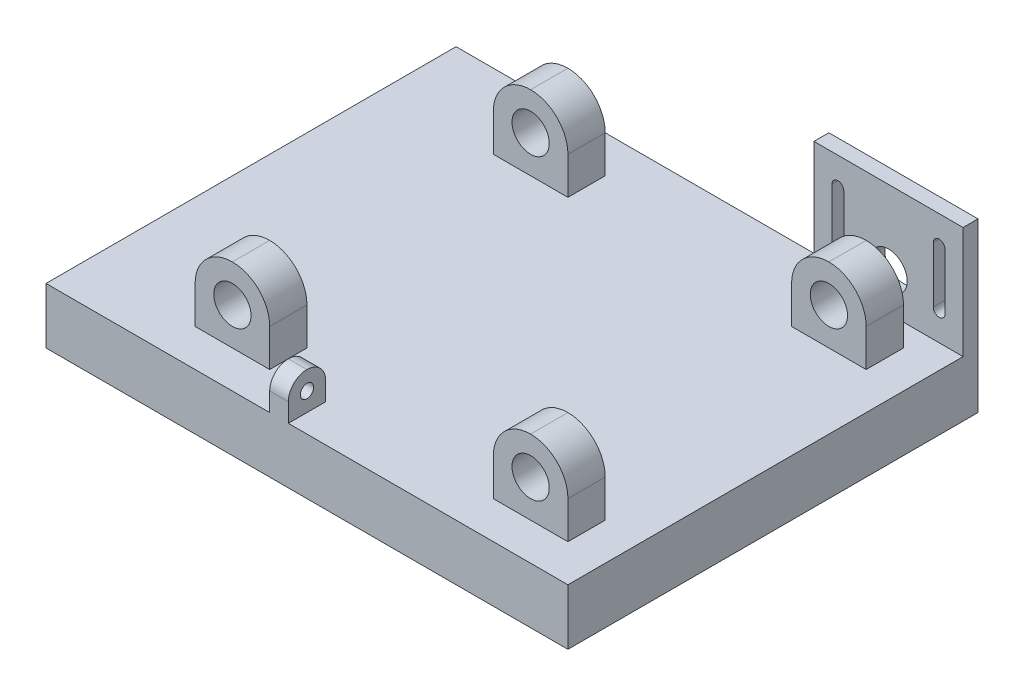
SolidWorks part; units mm, degrees
ref_plane "Front Plane" through (0, 0, 0) normal (0, 0, 1) x (1, 0, 0)
ref_plane "Top Plane" through (0, 0, 0) normal (0, 1, 0) x (1, 0, 0)
ref_plane "Right Plane" through (0, 0, 0) normal (1, 0, 0) x (0, 0, -1)
sketch "Sketch1" plane through (0, 0, 0) normal (0, 1, 0) x (1, 0, 0)
  line L1 (-88.9, -69.85) -> (88.9, -69.85)
  line L2 (-88.9, -69.85) -> (-88.9, 69.85)
  line L3 (-88.9, 69.85) -> (88.9, 69.85)
  line L4 (88.9, -69.85) -> (88.9, 69.85)
  line L5 (-88.9, -69.85) -> (88.9, 69.85) construction
  line L6 (-88.9, 69.85) -> (88.9, -69.85) construction
  point P0 (0, 0)
  dimension "D1" = 177.8
  dimension "D2" = 139.7
extrude "Boss-Extrude1" add sketch "Sketch1" along normal blind 19.05
sketch "Sketch3" plane through (0, 19.05, 0) normal (0, 1, 0) x (1, 0, 0)
  line L0 (-88.9, -69.85) -> (88.9, -69.85) construction
  line L1 (-50.8, 57.15) -> (-25.4, 57.15)
  line L2 (-50.8, 57.15) -> (-50.8, 44.45)
  line L3 (-50.8, 44.45) -> (-25.4, 44.45)
  line L4 (-25.4, 57.15) -> (-25.4, 44.45)
  line L5 (-50.8, 57.15) -> (-25.4, 44.45) construction
  line L6 (-50.8, 44.45) -> (-25.4, 57.15) construction
  line L7 (50.8, 57.15) -> (76.2, 57.15)
  line L8 (50.8, 57.15) -> (50.8, 44.45)
  line L9 (50.8, 44.45) -> (76.2, 44.45)
  line L10 (76.2, 57.15) -> (76.2, 44.45)
  line L11 (50.8, 57.15) -> (76.2, 44.45) construction
  line L12 (50.8, 44.45) -> (76.2, 57.15) construction
  line L13 (88.9, 69.85) -> (-88.9, 69.85) construction
  line L14 (-88.9, 69.85) -> (-88.9, -69.85) construction
  line L15 (88.9, -69.85) -> (88.9, 69.85) construction
  line L19 (-50.8, -44.45) -> (-25.4, -44.45)
  line L20 (-50.8, -44.45) -> (-50.8, -57.15)
  line L21 (-50.8, -57.15) -> (-25.4, -57.15)
  line L22 (-25.4, -44.45) -> (-25.4, -57.15)
  line L23 (-50.8, -44.45) -> (-25.4, -57.15) construction
  line L24 (-50.8, -57.15) -> (-25.4, -44.45) construction
  line L25 (50.8, -57.15) -> (76.2, -57.15)
  line L26 (50.8, -57.15) -> (50.8, -44.45)
  line L27 (50.8, -44.45) -> (76.2, -44.45)
  line L28 (76.2, -57.15) -> (76.2, -44.45)
  line L29 (50.8, -57.15) -> (76.2, -44.45) construction
  line L30 (50.8, -44.45) -> (76.2, -57.15) construction
  point P0 (-38.1, 50.8)
  point P5 (63.5, 50.8)
  point P10 (46.38, 48.3675)
  point P15 (-38.1, -50.8)
  point P20 (63.5, -50.8)
  dimension "D1" = 25.4
  dimension "D2" = 12.7
  dimension "D3" = 12.7
  dimension "D4" = 12.7
  dimension "D5" = 38.1
  dimension "D6" = 38.1
  dimension "D7" = 12.7
  dimension "D8" = 12.7
  dimension "D9" = 25.4
  dimension "D10" = 12.7
extrude "Boss-Extrude2" add sketch "Sketch3" along normal blind 25.4
sketch "Sketch5" plane through (0, 19.05, 0) normal (0, 1, 0) x (1, 0, 0)
  line L0 (88.9, -69.85) -> (88.9, 69.85) construction
  line L1 (38.1, 64.77) -> (88.9, 64.77)
  line L2 (38.1, 64.77) -> (38.1, 69.85)
  line L3 (38.1, 69.85) -> (88.9, 69.85)
  line L4 (88.9, 64.77) -> (88.9, 69.85)
  line L5 (38.1, 64.77) -> (88.9, 69.85) construction
  line L6 (38.1, 69.85) -> (88.9, 64.77) construction
  line L7 (88.9, 69.85) -> (-88.9, 69.85) construction
  point P0 (63.5, 67.31)
  dimension "D1" = 50.8
  dimension "D2" = 0
  dimension "D3" = 5.08
  dimension "D4" = 0
extrude "Boss-Extrude3" add sketch "Sketch5" along normal blind 38.1
sketch "Sketch4" plane through (0, 0, 44.45) normal (0, 0, -1) x (-1, 0, 0)
  line L0 (50.8, 44.45) -> (25.4, 44.45) construction
  line L1 (25.4, 44.45) -> (25.4, 19.05) construction
  line L2 (-76.2, 44.45) -> (-76.2, 19.05) construction
  line L3 (-50.8, 19.05) -> (-76.2, 19.05) construction
  circle A0 centre (38.1, 31.75) radius 6.35
  circle A1 centre (-63.5, 31.75) radius 6.35
  dimension "D1" = 12.7
  dimension "D2" = 12.7
  dimension "D3" = 12.7
  dimension "D4" = 12.7
  dimension "D5" = 12.7
  dimension "D6" = 12.7
extrude "Cut-Extrude1" cut sketch "Sketch4" against normal through all both and the other way through all
sketch "Sketch6" plane through (0, 0, -69.85) normal (0, 0, -1) x (-1, 0, 0)
  line L0 (-46.25, 28.575) -> (-46.25, 47.625) construction
  line L1 (-48.25, 28.575) -> (-48.25, 47.625)
  line L2 (-44.25, 28.575) -> (-44.25, 47.625)
  line L3 (-80.75, 28.575) -> (-80.75, 47.625) construction
  line L4 (-82.75, 28.575) -> (-82.75, 47.625)
  line L5 (-78.75, 28.575) -> (-78.75, 47.625)
  line L8 (-88.9, 57.15) -> (-88.9, 0) construction
  line L10 (88.9, 19.05) -> (-38.1, 19.05) construction
  line L11 (-44.25, 28.575) -> (-38.1, 28.575)
  line L13 (-38.1, 57.15) -> (-38.1, 19.05) construction
  line L14 (-88.9, 28.575) -> (-82.75, 28.575)
  arc A0 (-48.25, 28.575) -> (-44.25, 28.575) centre (-46.25, 28.575) ccw
  arc A1 (-44.25, 47.625) -> (-48.25, 47.625) centre (-46.25, 47.625) ccw
  arc A2 (-82.75, 28.575) -> (-78.75, 28.575) centre (-80.75, 28.575) ccw
  arc A3 (-78.75, 47.625) -> (-82.75, 47.625) centre (-80.75, 47.625) ccw
  point P2 (-46.25, 38.1)
  point P7 (-80.75, 38.1)
  dimension "D1" = 34.5
  dimension "D2" = 19.05
  dimension "D3" = 19.05
  dimension "D4" = 9.525
  dimension "D5" = 9.525
  dimension "D6" = 4
  dimension "D8" = 4
extrude "Cut-Extrude2" cut sketch "Sketch6" against normal up to next contours L1 A1 L2 A0 | L5 A3 L4 A2
sketch "Sketch7" plane through (0, 19.05, 0) normal (0, 1, 0) x (1, 0, 0)
  line L1 (-12.7, -69.85) -> (-6.35, -69.85)
  line L2 (-12.7, -69.85) -> (-12.7, -57.15)
  line L3 (-12.7, -57.15) -> (-6.35, -57.15)
  line L4 (-6.35, -69.85) -> (-6.35, -57.15)
  line L5 (-12.7, -69.85) -> (-6.35, -57.15) construction
  line L6 (-12.7, -57.15) -> (-6.35, -69.85) construction
  line L7 (-25.4, -44.45) -> (-25.4, -57.15) construction
  line L8 (-50.8, -57.15) -> (-25.4, -57.15) construction
  point P0 (-9.525, -63.5)
  dimension "D1" = 0
  dimension "D2" = 12.7
  dimension "D3" = 6.35
  dimension "D4" = 12.7
extrude "Boss-Extrude4" add sketch "Sketch7" along normal blind 12.7
fillet "Fillet1" radius 12.7 8 edges at (76.2, 44.45, -50.8) (50.8, 44.45, -50.8) (76.2, 44.45, 50.8) (50.8, 44.45, 50.8) (-25.4, 44.45, 50.8) (-50.8, 44.45, 50.8) (-25.4, 44.45, -50.8) (-50.8, 44.45, -50.8)
sketch "Sketch8" plane through (-6.35, 0, 0) normal (1, 0, 0) x (0, 0, -1)
  line L0 (-57.15, 31.75) -> (-57.15, 19.05) construction
  line L1 (-69.85, 31.75) -> (-57.15, 31.75) construction
  circle A0 centre (-63.5, 25.4) radius 2.2803
  point P4 (-63.5, 31.75)
  dimension "D2" = 6.35
  dimension "D1" = 6.35
extrude "Cut-Extrude3" cut sketch "Sketch8" against normal up to next
fillet "Fillet2" radius 6.35 2 edges at (-9.525, 31.75, 57.15) (-9.525, 31.75, 69.85)
